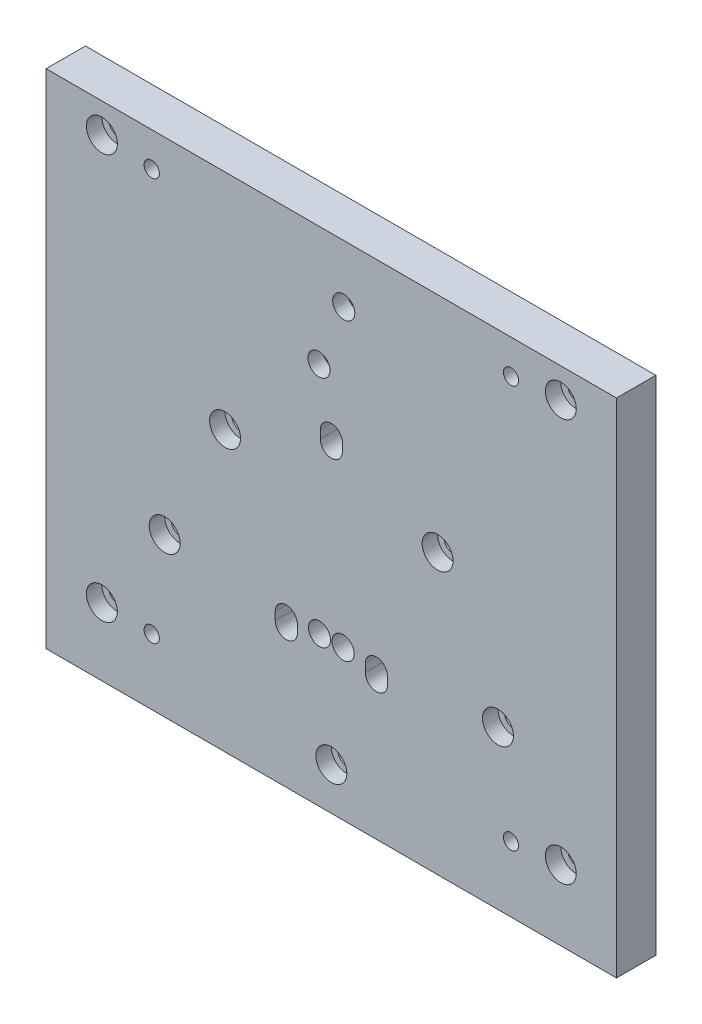
SolidWorks part; units mm, degrees
material "Beech"
ref_plane "Front Plane" through (0, 0, 0) normal (0, 0, 1) x (1, 0, 0)
ref_plane "Top Plane" through (0, 0, 0) normal (0, 1, 0) x (1, 0, 0)
ref_plane "Right Plane" through (0, 0, 0) normal (1, 0, 0) x (0, 0, -1)
sketch "Sketch1" plane through (0, 0, 0) normal (0, 0, 1) x (1, 0, 0)
  line L1 (2.065, -202.025) -> (-182.085, -202.025)
  line L2 (2.065, -202.025) -> (2.065, -55.975)
  line L3 (2.065, -55.975) -> (-182.085, -55.975)
  line L4 (-182.085, -202.025) -> (-182.085, -55.975)
  line L5 (2.065, -202.025) -> (-182.085, -55.975) construction
  line L6 (2.065, -55.975) -> (-182.085, -202.025) construction
  point P0 (-90.01, -129)
  dimension "D1" = 184.15
  dimension "D2" = 146.05
extrude "Boss-Extrude1" add sketch "Sketch1" along normal blind 12.7
ref_plane "CL" through (0, -129, 0) normal (0, -1, 0) x (-1, 0, 0)
sketch "Sketch5" plane through (0, -202.025, 0) normal (0, -1, 0) x (1, 0, 0)
  line L4 (-182.085, 0) -> (2.065, 0)
  line L5 (2.065, 0) -> (2.065, 12.7)
  line L6 (2.065, 12.7) -> (-182.085, 12.7)
  line L7 (-182.085, 12.7) -> (-182.085, 0)
  line L8 (-182.085, 0) -> (2.065, 0)
  line L9 (2.065, 0) -> (2.065, 12.7)
  line L10 (2.065, 12.7) -> (-182.085, 12.7)
  line L11 (-182.085, 12.7) -> (-182.085, 0)
  dimension "D1" = 0
extrude "Boss-Extrude2" add sketch "Sketch5" along normal up to surface (16.125 mm away)
hole_wizard "CBORE for M5 SHCS2" positions "Sketch2" profile "Sketch3" counterbore size "M5" standard "ANSI Metric" end condition up to next
sketch "Sketch2" plane through (0, 0, 12.7) normal (0, 0, 1) x (1, 0, 0)
  point P0 (-55.7, -127.9887)
  point P2 (-124.32, -127.9887)
  point P17 (-90.01, -204.5313)
  point P19 (-143.8109, -167.1)
  point P21 (-36.2091, -167.1)
sketch "Sketch3" plane through (-55.7, -127.9887, 12.7) normal (1, 0, 0) x (0, -1, 0)
  line L0 (0, 0) -> (0, 12.7)
  line L1 (0, 12.7) -> (2.9, 12.7)
  line L3 (2.9, 12.7) -> (2.9, 5)
  line L4 (2.9, 5) -> (5, 5)
  line L5 (5, 5) -> (5, 0)
  line L7 (5, 0) -> (0, 0)
  line L11 (0, -6.35) -> (0, 107.95) construction
  dimension "Thru Hole Dia." = 5.8
  dimension "Thru Hole Depth" = 12.7
  dimension "C'Bore Dia." = 10
  dimension "C'Bore Depth" = 5
hole_wizard "CBORE for M5 SHCS3" positions "Sketch6" profile "Sketch7" counterbore size "M5" standard "ANSI Metric" end condition through all
sketch "Sketch6" plane through (0, 0, 12.7) normal (0, 0, 1) x (1, 0, 0)
  point P0 (-15.925, -65.5)
  point P2 (-15.925, -195.4887)
  point P4 (-164.095, -196.2787)
  point P6 (-164.095, -65.5)
sketch "Sketch7" plane through (-15.925, -65.5, 12.7) normal (1, 0, 0) x (0, -1, 0)
  line L0 (0, 0) -> (0, 12.7)
  line L1 (0, 12.7) -> (2.65, 12.7)
  line L3 (2.65, 12.7) -> (2.65, 5)
  line L4 (2.65, 5) -> (5, 5)
  line L5 (5, 5) -> (5, 0)
  line L7 (5, 0) -> (0, 0)
  line L11 (0, -6.35) -> (0, 107.95) construction
  dimension "Thru Hole Dia." = 5.3
  dimension "Thru Hole Depth" = 12.7
  dimension "C'Bore Dia." = 10
  dimension "C'Bore Depth" = 5
sketch "Sketch12" plane through (0, 0, 0) normal (0, 0, -1) x (-1, 0, 0)
  circle A0 centre (164.095, -65.5) radius 5
  circle A1 centre (164.095, -196.2787) radius 5
  dimension "D1" = 10
extrude "Cut-Extrude1" cut sketch "Sketch12" against normal blind 2.54
hole_wizard "CBORE SLOT for #6 Socket Head Cap Screw1" positions "Sketch15" profile "Sketch16" size "#6" standard "ANSI Inch" slot yes end condition through all
sketch "Sketch15" plane through (0, 0, 12.7) normal (0, 0, 1) x (1, 0, 0)
  line L0 (-90.01, -117.15) -> (-90.01, -110.8) construction
  line L1 (-90.01, -218.15) -> (-90.01, -55.975) construction
  line L2 (-182.085, -218.15) -> (2.065, -218.15) construction
  line L3 (2.065, -55.975) -> (-182.085, -55.975) construction
  point P0 (-90.01, -113.975)
  point P6 (-104.5514, -171.9951)
  point P17 (-75.4686, -171.9951)
  dimension "D1" = 6.35
sketch "Sketch16" plane through (-90.01, -113.975, 12.7) normal (1, 0, 0) x (0, -1, 0)
  line L0 (0, 0) -> (0, 12.7)
  line L1 (0, 12.7) -> (1.8986, 12.7)
  line L3 (1.8986, 12.7) -> (1.8986, 7.3152)
  line L4 (1.8986, 7.3152) -> (3.5725, 7.3152)
  line L5 (3.5725, 7.3152) -> (3.5725, 0)
  line L7 (3.5725, 0) -> (0, 0)
  line L11 (0, -6.35) -> (0, 107.95) construction
  dimension "Thru Hole Dia." = 3.7973
  dimension "Thru Hole Depth" = 12.7
  dimension "C'Bore Dia." = 7.145
  dimension "C'Bore Depth" = 7.3152
hole_wizard "CBORE for #6 Socket Head Cap Screw1" positions "Sketch19" profile "Sketch18" counterbore size "#6" standard "ANSI Inch" end condition through all
sketch "Sketch19" plane through (0, 0, 12.7) normal (0, 0, 1) x (1, 0, 0)
  line L0 (-90.01, -218.15) -> (-90.01, -55.975) construction
  line L1 (-182.085, -218.15) -> (2.065, -218.15) construction
  line L2 (2.065, -55.975) -> (-182.085, -55.975) construction
  point P0 (-93.82, -169.8501)
  point P15 (-86.2, -169.8501)
  dimension "D1" = 48.2999
  dimension "D2" = 3.81
sketch "Sketch18" plane through (-93.82, -169.8501, 12.7) normal (1, 0, 0) x (0, -1, 0)
  line L0 (0, 0) -> (0, 12.7)
  line L1 (0, 12.7) -> (2.1526, 12.7)
  line L3 (2.1526, 12.7) -> (2.1526, 7.3152)
  line L4 (2.1526, 7.3152) -> (3.5725, 7.3152)
  line L5 (3.5725, 7.3152) -> (3.5725, 0)
  line L7 (3.5725, 0) -> (0, 0)
  line L11 (0, -6.35) -> (0, 107.95) construction
  dimension "Thru Hole Dia." = 4.3053
  dimension "Thru Hole Depth" = 12.7
  dimension "C'Bore Dia." = 7.145
  dimension "C'Bore Depth" = 7.3152
hole_wizard "#8 Clearance Hole1" positions "Sketch20" profile "Sketch21" hole size "#8" standard "ANSI Inch" end condition through all
sketch "Sketch20" plane through (0, 0, 12.7) normal (0, 0, 1) x (1, 0, 0)
  point P0 (-32.01, -66.9887)
  point P4 (-148.01, -66.9887)
  point P6 (-148.01, -196.9887)
  point P8 (-32.01, -196.9887)
sketch "Sketch21" plane through (-32.01, -66.9887, 12.7) normal (1, 0, 0) x (0, -1, 0)
  line L0 (0, 0) -> (0, 12.7)
  line L1 (0, 12.7) -> (2.4574, 12.7)
  line L2 (2.4574, 12.7) -> (2.4574, 0)
  line L5 (2.4574, 0) -> (0, 0)
  line L11 (0, -6.35) -> (0, 107.95) construction
  dimension "Thru Hole Dia." = 4.9149
  dimension "Thru Hole Depth" = 12.7
hole_wizard "CBORE for #6 Socket Head Cap Screw2" positions "Sketch22" profile "Sketch23" counterbore size "#6" standard "ANSI Inch" end condition through all
sketch "Sketch22" plane through (0, 0, 12.7) normal (0, 0, 1) x (1, 0, 0)
  point P0 (-94.01, -94.5397)
  point P2 (-86.01, -74.5397)
sketch "Sketch23" plane through (-94.01, -94.5397, 12.7) normal (1, 0, 0) x (0, -1, 0)
  line L0 (0, 0) -> (0, 12.7)
  line L1 (0, 12.7) -> (2.1527, 12.7)
  line L3 (2.1527, 12.7) -> (2.1526, 4.7752)
  line L4 (2.1526, 4.7752) -> (3.5725, 4.7752)
  line L5 (3.5725, 4.7752) -> (3.5725, 0)
  line L7 (3.5725, 0) -> (0, 0)
  line L11 (0, -6.35) -> (0, 107.95) construction
  dimension "Thru Hole Dia." = 4.3053
  dimension "Thru Hole Depth" = 12.7
  dimension "C'Bore Dia." = 7.145
  dimension "C'Bore Depth" = 4.7752
sketch "Sketch24" plane through (0, 0, 0) normal (0, 0, -1) x (-1, 0, 0)
  circle A0 centre (148.01, -66.9887) radius 9.525
  circle A1 centre (32.01, -66.9887) radius 9.525
  circle A2 centre (32.01, -196.9887) radius 9.525
  circle A3 centre (148.01, -196.9887) radius 9.525
  dimension "D1" = 19.05
extrude "Cut-Extrude2" cut sketch "Sketch24" against normal blind 3.175
